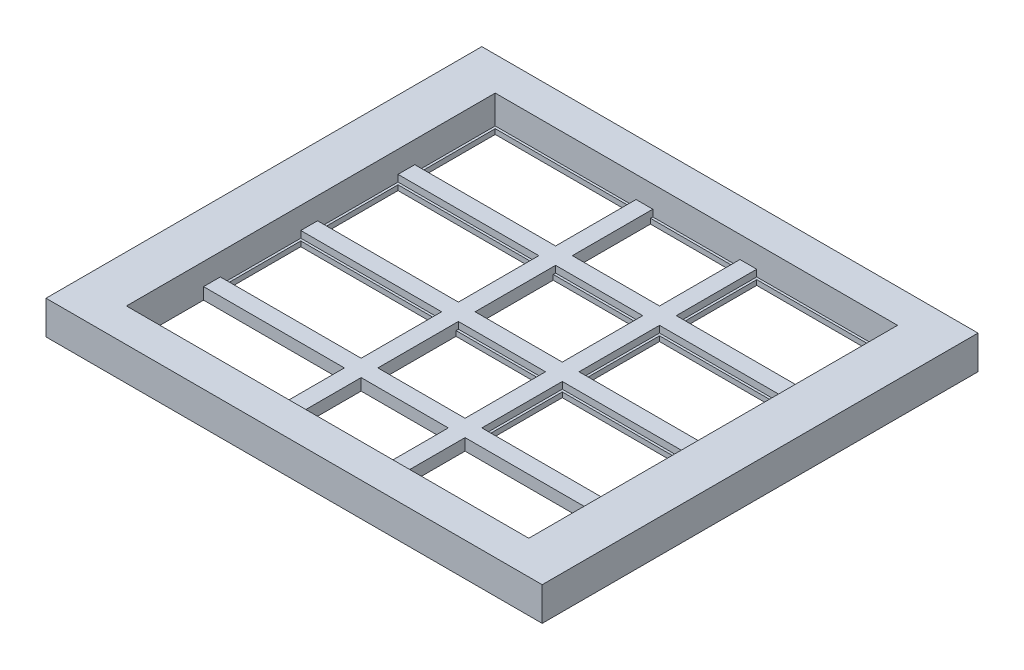
SolidWorks part; units mm, degrees
ref_plane "Front Plane" through (0, 0, 0) normal (0, 0, 1) x (1, 0, 0)
ref_plane "Top Plane" through (0, 0, 0) normal (0, 1, 0) x (1, 0, 0)
ref_plane "Right Plane" through (0, 0, 0) normal (1, 0, 0) x (0, 0, -1)
sketch "Sketch1" plane through (0, 0, 0) normal (0, 1, 0) x (1, 0, 0)
  line L0 (36.2173, -16.1456) -> (36.2173, 113.8544)
  line L1 (50.2173, -6.1456) -> (50.2173, 103.8544)
  line L2 (170.2173, -6.1456) -> (170.2173, 103.8544)
  line L3 (184.2173, -16.1456) -> (184.2173, 113.8544)
  line L4 (36.2173, 113.8544) -> (184.2173, 113.8544)
  line L5 (184.2173, -16.1456) -> (36.2173, -16.1456)
  line L10 (50.2173, 103.8544) -> (170.2173, 103.8544)
  line L12 (170.2173, -6.1456) -> (50.2173, -6.1456)
  line L14 (46.2173, 103.8544) -> (174.2173, 103.8544) construction
  line L15 (174.2173, -6.1456) -> (46.2173, -6.1456) construction
  line L16 (50.2173, -16.1456) -> (50.2173, 113.8544) construction
  line L17 (170.2173, -16.1456) -> (170.2173, 113.8544) construction
  line L18 (46.2173, -6.1456) -> (46.2173, 103.8544) construction
  line L19 (174.2173, -6.1456) -> (174.2173, 103.8544) construction
  line L20 (50.2173, 79.8544) -> (170.2173, 79.8544)
  line L24 (74.2173, 17.8544) -> (74.2173, 79.8544) construction
  line L25 (146.2173, 17.8544) -> (146.2173, 79.8544) construction
  line L26 (146.2173, 17.8544) -> (74.2173, 17.8544) construction
  line L27 (74.2173, 79.8544) -> (146.2173, 79.8544) construction
  line L28 (50.2173, 74.8544) -> (170.2173, 74.8544)
  line L29 (50.2173, 50.8544) -> (170.2173, 50.8544)
  line L30 (50.2173, 45.8544) -> (170.2173, 45.8544)
  line L31 (50.2173, 21.8544) -> (170.2173, 21.8544)
  line L32 (50.2173, 16.8544) -> (170.2173, 16.8544)
  dimension "D1" = 14
  dimension "D2" = 134
  dimension "D3" = 24
  dimension "D4" = 10
  dimension "D5" = 5
  dimension "D6" = 29
  dimension "D7" = 29
extrude "Boss-Extrude2" add sketch "Sketch1" along normal blind 10 contours L5 L3 L4 L0 L2 L12 L1 L10 region at (38.1872, 0, -48.8544)
sketch "Sketch2" plane through (0, 0, 0) normal (0, -1, 0) x (1, 0, 0)
  line L0 (50.2173, -103.8544) -> (170.2173, -103.8544)
  line L1 (50.2173, -103.8544) -> (170.2173, -103.8544) construction
  line L2 (50.2173, 6.1456) -> (170.2173, 6.1456)
  line L3 (170.2173, 6.1456) -> (170.2173, -103.8544) construction
  line L4 (170.2173, 6.1456) -> (50.2173, 6.1456) construction
  line L5 (50.2173, -103.8544) -> (50.2173, 6.1456)
  line L6 (50.2173, 6.1456) -> (50.2173, -103.8544) construction
  line L7 (170.2173, -103.8544) -> (170.2173, 6.1456)
  line L8 (74.2173, -79.8544) -> (146.2173, -79.8544) construction
  line L9 (50.2173, -79.8544) -> (170.2173, -79.8544)
  line L10 (50.2173, -74.8544) -> (170.2173, -74.8544)
  line L11 (74.2173, -79.8544) -> (74.2173, 6.1456) construction
  line L12 (146.2173, -79.8544) -> (146.2173, 6.1456) construction
  line L13 (50.2173, -50.8544) -> (170.2173, -50.8544)
  line L14 (50.2173, -45.8544) -> (170.2173, -45.8544)
  line L15 (50.2173, -21.8544) -> (170.2173, -21.8544)
  line L16 (50.2173, -16.8544) -> (170.2173, -16.8544)
  line L17 (50.9173, -103.1544) -> (169.5173, -103.1544)
  line L18 (169.5173, -103.1544) -> (169.5173, -80.5544)
  line L19 (50.9173, 5.4456) -> (169.5173, 5.4456)
  line L20 (50.9173, -103.1544) -> (50.9173, -80.5544)
  line L21 (50.9173, -74.1544) -> (169.5173, -74.1544)
  line L22 (50.9173, -45.1544) -> (169.5173, -45.1544)
  line L23 (50.9173, -16.1544) -> (169.5173, -16.1544)
  line L24 (50.9173, -80.5544) -> (169.5173, -80.5544)
  line L25 (50.9173, -51.5544) -> (169.5173, -51.5544)
  line L26 (50.9173, -22.5544) -> (169.5173, -22.5544)
  line L27 (50.9173, -74.1544) -> (50.9173, -51.5544)
  line L28 (50.9173, -103.1544) -> (50.9173, 5.4456) construction
  line L29 (50.2173, -74.1544) -> (170.2173, -74.1544) construction
  line L30 (50.2173, -80.5544) -> (170.2173, -80.5544) construction
  line L31 (169.5173, -74.1544) -> (169.5173, -51.5544)
  line L32 (169.5173, -103.1544) -> (169.5173, 5.4456) construction
  line L33 (50.2173, -51.5544) -> (170.2173, -51.5544) construction
  line L34 (169.5173, -45.1544) -> (169.5173, -22.5544)
  line L35 (50.2173, -45.1544) -> (170.2173, -45.1544) construction
  line L36 (50.9173, -45.1544) -> (50.9173, -22.5544)
  line L37 (50.2173, -22.5544) -> (170.2173, -22.5544) construction
  line L38 (169.5173, -16.1544) -> (169.5173, 5.4456)
  line L39 (50.2173, -16.1544) -> (170.2173, -16.1544) construction
  line L40 (50.9173, -16.1544) -> (50.9173, 5.4456)
  line M22 (170.2173, 6.1456) -> (170.2173, -103.8544)
  line M23 (170.2173, -103.8544) -> (50.2173, -103.8544)
  line M24 (50.2173, -103.8544) -> (50.2173, 6.1456)
  line M25 (50.2173, 6.1456) -> (170.2173, 6.1456)
  dimension "D1" = 24
  dimension "D2" = 5
  dimension "D3" = 29
  dimension "D4" = 29
  dimension "D5" = 0.7
  dimension "D6" = 0.7
extrude "Boss-Extrude3" add sketch "Sketch2" against normal blind 1.5 contours L9 L7 L20 L24 L18 L17 M24 M23 | L13 L10 L7 L31 L21 L27 L25 M24 | L15 L14 L7 L22 L36 L26 L34 M24 | L16 L23 L40 L19 L38 M24 M22 M25 | L16 L5 L15 L7 | L14 L5 L13 L7 | L10 L5 L9 L7 region at (50.3397, 0, -91.8544) region at (110.2173, 0, -77.3544) region at (50.3397, 0, -62.8544) region at (110.2173, 0, -48.3544) region at (50.3397, 0, -33.8544) region at (110.2173, 0, -19.3544) region at (50.3395, 0, -5.3544)
sketch "Sketch3" plane through (0, 1.5, 0) normal (0, 1, 0) x (1, 0, 0)
  line L0 (50.2173, 74.8544) -> (170.2173, 74.8544)
  line L3 (50.2173, 79.8544) -> (170.2173, 79.8544)
  line L4 (50.2173, 79.8544) -> (50.2173, 74.8544)
  line L5 (170.2173, 79.8544) -> (170.2173, 74.8544)
  line L6 (50.2173, 45.8544) -> (50.2173, 50.8544)
  line L9 (170.2173, 45.8544) -> (50.2173, 45.8544)
  line L10 (50.2173, 103.8544) -> (50.2173, -6.1456) construction
  line L11 (170.2173, 45.8544) -> (170.2173, 50.8544)
  line L12 (170.2173, -6.1456) -> (170.2173, 103.8544) construction
  line L13 (170.2173, 50.8544) -> (50.2173, 50.8544)
  line L14 (50.2173, 16.8544) -> (50.2173, 21.8544)
  line L16 (170.2173, 16.8544) -> (50.2173, 16.8544)
  line L17 (170.2173, 16.8544) -> (170.2173, 21.8544)
  line L18 (170.2173, -6.1456) -> (170.2173, 103.8544) construction
  line L19 (170.2173, 21.8544) -> (50.2173, 21.8544)
  dimension "D1" = 5
extrude "Boss-Extrude4" add sketch "Sketch3" along normal blind 2 contours L19 L14 L16 L17 | L13 L6 L9 L11 | L5 L0 L4 L3
sketch "Sketch4" plane through (0, 0, 0) normal (0, -1, 0) x (-1, 0, 0)
  line L0 (-50.2173, 103.8544) -> (-50.2173, -6.1456)
  line L1 (-170.2173, -6.1456) -> (-50.2173, -6.1456) construction
  line L2 (-50.2173, -6.1456) -> (-50.2173, 103.8544) construction
  line L3 (-92.2173, 103.8544) -> (-92.2173, -6.1456)
  line L4 (-87.2173, 103.8544) -> (-87.2173, -6.1456)
  line L5 (-87.2173, 103.8544) -> (-92.2173, 103.8544)
  line L6 (-92.2173, -6.1456) -> (-87.2173, -6.1456)
  line L7 (-170.2173, -6.1456) -> (-170.2173, 103.8544)
  line L8 (-128.2173, -6.1456) -> (-128.2173, 103.8544)
  line L9 (-123.2173, -6.1456) -> (-123.2173, 103.8544)
  line L10 (-123.2173, 103.8544) -> (-128.2173, 103.8544)
  line L11 (-128.2173, -6.1456) -> (-123.2173, -6.1456)
  dimension "D1" = 42
  dimension "D2" = 5
  dimension "D3" = 42
  dimension "D4" = 5
extrude "Boss-Extrude5" add sketch "Sketch4" against normal blind 3.5 contours L4 L6 L3 L5 | L9 L10 L8 L11
sketch "Sketch5" plane through (0, 0, 0) normal (0, -1, 0) x (-1, 0, 0)
  line L1 (-92.2173, 80.5544) -> (-92.2173, 103.1544)
  line L2 (-92.2173, 103.1544) -> (-87.2173, 103.1544)
  line L14 (-87.2173, 16.1544) -> (-92.2173, 16.1544)
  line L15 (-92.2173, 16.8544) -> (-92.2173, -6.1456) construction
  line L16 (-92.2173, 16.1544) -> (-92.2173, -5.4456)
  line L17 (-92.2173, -5.4456) -> (-87.2173, -5.4456)
  line L18 (-87.2173, 16.8544) -> (-87.2173, -6.1456) construction
  line L19 (-87.2173, -5.4456) -> (-87.2173, 16.1544)
  line L21 (-87.2173, 22.5544) -> (-92.2173, 22.5544)
  line L22 (-92.2173, 22.5544) -> (-92.2173, 45.1544)
  line L23 (-92.2173, 45.1544) -> (-87.2173, 45.1544)
  line L24 (-87.2173, 103.1544) -> (-87.2173, 80.5544)
  line L25 (-87.2173, 22.5544) -> (-87.2173, 45.1544)
  line L26 (-87.2173, 51.5544) -> (-92.2173, 51.5544)
  line L27 (-92.2173, 51.5544) -> (-92.2173, 74.1544)
  line L28 (-92.2173, 74.1544) -> (-87.2173, 74.1544)
  line L29 (-87.2173, 74.1544) -> (-87.2173, 51.5544)
  line L30 (-87.2173, 80.5544) -> (-92.2173, 80.5544)
extrude "Cut-Extrude1" cut sketch "Sketch5" against normal blind 10
sketch "Sketch6" plane through (0, 1.5, 0) normal (0, 1, 0) x (1, 0, 0)
  line L0 (87.2173, 103.8544) -> (92.2173, 103.8544)
  line L1 (92.2173, 103.8544) -> (92.2173, 103.1544)
  line L2 (92.2173, 103.8544) -> (92.2173, 103.1544) construction
  line L3 (92.2173, 103.1544) -> (87.2173, 103.1544) construction
  line L4 (92.2173, 103.1544) -> (87.2173, 103.1544)
  line L5 (87.2173, 103.1544) -> (87.2173, 103.8544)
  line L6 (92.2173, 80.5544) -> (87.2173, 80.5544)
  line L7 (87.2173, 80.5544) -> (87.2173, 79.8544)
  line L8 (87.2173, 79.8544) -> (92.2173, 79.8544)
  line L9 (92.2173, 79.8544) -> (92.2173, 80.5544)
  line L10 (87.2173, 74.8544) -> (92.2173, 74.8544)
  line L11 (92.2173, 74.8544) -> (92.2173, 74.1544)
  line L12 (92.2173, 74.1544) -> (87.2173, 74.1544) construction
  line L13 (92.2173, 74.1544) -> (123.2173, 74.1544) construction
  line L14 (92.2173, 74.1544) -> (87.2173, 74.1544)
  line L15 (87.2173, 74.8544) -> (87.2173, 74.1544) construction
  line L16 (87.2173, 74.1544) -> (87.2173, 74.8544)
  line L17 (87.2173, 51.5544) -> (92.2173, 51.5544)
  line L18 (92.2173, 51.5544) -> (92.2173, 50.8544)
  line L19 (92.2173, 50.8544) -> (87.2173, 50.8544)
  line L20 (87.2173, 50.8544) -> (87.2173, 51.5544)
  line L21 (92.2173, 45.8544) -> (87.2173, 45.8544)
  line L22 (87.2173, 45.8544) -> (87.2173, 45.1544)
  line L23 (92.2173, 45.1544) -> (87.2173, 45.1544) construction
  line L24 (87.2173, 45.1544) -> (92.2173, 45.1544)
  line L25 (92.2173, 45.1544) -> (92.2173, 45.8544)
  line L26 (87.2173, 22.5544) -> (92.2173, 22.5544)
  line L27 (92.2173, 22.5544) -> (92.2173, 21.8544)
  line L28 (92.2173, 21.8544) -> (87.2173, 21.8544)
  line L29 (87.2173, 21.8544) -> (87.2173, 22.5544)
  line L30 (87.2173, 16.8544) -> (92.2173, 16.8544)
  line L31 (92.2173, 16.8544) -> (92.2173, 16.1544)
  line L32 (92.2173, 16.1544) -> (87.2173, 16.1544) construction
  line L33 (92.2173, 16.1544) -> (87.2173, 16.1544)
  line L34 (87.2173, 16.8544) -> (87.2173, 16.1544) construction
  line L35 (87.2173, 16.1544) -> (87.2173, 16.8544)
  line L36 (87.2173, -5.4456) -> (92.2173, -5.4456)
  line L37 (92.2173, -5.4456) -> (92.2173, -6.1456)
  line L38 (92.2173, -6.1456) -> (87.2173, -6.1456)
  line L39 (87.2173, -6.1456) -> (87.2173, -5.4456)
extrude "Cut-Extrude2" cut sketch "Sketch6" along normal blind 2
sketch "Sketch7" plane through (0, 0, 0) normal (0, -1, 0) x (-1, 0, 0)
  line L0 (-92.2173, 79.8544) -> (-97.2173, 79.8544)
  line L3 (-92.2173, 103.8544) -> (-92.2173, 79.8544)
  line L4 (-97.2173, 103.8544) -> (-97.2173, 79.8544)
  line L5 (-97.2173, 103.8544) -> (-92.2173, 103.8544)
  line L6 (-92.2173, 74.8544) -> (-92.2173, 50.8544)
  line L7 (-97.2173, 74.8544) -> (-97.2173, 50.8544)
  line L8 (-92.2173, 50.8544) -> (-97.2173, 50.8544)
  line L9 (-97.2173, 74.8544) -> (-92.2173, 74.8544)
  line L10 (-97.2173, 16.8544) -> (-97.2173, -6.1456)
  line L11 (-97.2173, 16.8544) -> (-92.2173, 16.8544)
  line L12 (-92.2173, 21.8544) -> (-97.2173, 21.8544)
  line L13 (-97.2173, 45.8544) -> (-92.2173, 45.8544)
  line L15 (-97.2173, 45.8544) -> (-97.2173, 21.8544)
  line L16 (-92.2173, 16.8544) -> (-92.2173, -6.1706)
  line L17 (-92.2173, 45.8544) -> (-92.2173, 21.8544)
  line L18 (-92.2173, -6.1706) -> (-97.2173, -6.1456)
  line L19 (-50.2173, -6.1456) -> (-123.2173, -6.1456) construction
  dimension "D2" = 5
extrude "Boss-Extrude7" add sketch "Sketch7" against normal blind 3.5
sketch "Sketch8" plane through (0, 0, 0) normal (0, -1, 0) x (-1, 0, 0)
  line L0 (-92.2173, 103.1544) -> (-92.2173, 80.5544)
  line L1 (-92.2173, 103.1544) -> (-91.5173, 103.1544)
  line L2 (-50.9173, 103.1544) -> (-92.2173, 103.1544) construction
  line L3 (-91.5173, 103.1544) -> (-91.5173, 80.5544)
  line L4 (-50.9173, 80.5544) -> (-92.2173, 80.5544) construction
  line L5 (-91.5173, 80.5544) -> (-92.2173, 80.5544)
  line L6 (-91.5173, 74.1544) -> (-91.5173, 51.5544)
  line L7 (-92.2173, 74.1544) -> (-91.5173, 74.1544)
  line L8 (-91.5173, 51.5544) -> (-92.2173, 51.5544)
  line L9 (-92.2173, 74.1544) -> (-92.2173, 51.5544)
  line L10 (-91.5173, 22.5544) -> (-92.2173, 22.5544)
  line L11 (-92.2173, 45.1544) -> (-92.2173, 22.5544)
  line L12 (-92.2173, 45.1544) -> (-91.5173, 45.1544)
  line L13 (-91.5173, 45.1544) -> (-91.5173, 22.5544)
extrude "Boss-Extrude8" add sketch "Sketch8" against normal blind 1.5
sketch "Sketch9" plane through (0, 0, 0) normal (0, -1, 0) x (-1, 0, 0)
  line L14 (-50.2173, 16.8544) -> (-92.2173, 16.8544)
  line L15 (-170.2173, -6.1456) -> (-170.2173, 103.8544) construction
  line L16 (-170.2173, 16.8544) -> (-128.2173, 16.8544) construction
  line L36 (-170.2173, -6.1456) -> (-128.2173, -6.1456)
  line L37 (-50.2173, -6.1456) -> (-92.2173, -6.1456) construction
  line L40 (-170.2173, -6.1456) -> (-50.2173, -6.1456) construction
  line L41 (-170.2173, -6.1456) -> (-170.2173, 16.8544)
  line L42 (-50.2173, 16.8544) -> (-50.2173, -6.1456)
  line L43 (-50.9173, 16.1544) -> (-92.2173, 16.1544)
  line L44 (-92.2173, 16.1544) -> (-92.2173, 16.8544)
  line L45 (-92.2173, -6.1456) -> (-92.2173, -5.4456)
  line L46 (-92.2173, -5.4456) -> (-50.9173, -5.4456)
  line L47 (-50.9173, -5.4456) -> (-50.9173, 16.1544)
  line L48 (-97.2173, 16.8544) -> (-97.2173, 16.1544)
  line L49 (-97.2173, 16.1544) -> (-123.2173, 16.1544)
  line L50 (-123.2173, 16.1544) -> (-123.2173, 16.8544)
  line L51 (-123.2173, -5.4456) -> (-97.2173, -5.4456)
  line L52 (-97.2173, -5.4456) -> (-97.2173, -6.1456)
  line L53 (-97.2173, 16.8544) -> (-97.2173, -6.1456) construction
  line L54 (-97.2173, -6.1456) -> (-123.2173, -6.1456)
  line L55 (-123.2173, -6.1456) -> (-123.2173, 16.8544) construction
  line L56 (-123.2173, -6.1456) -> (-123.2173, -5.4456)
  line L57 (-128.2173, 16.8544) -> (-128.2173, 16.1544)
  line L58 (-128.2173, 16.1544) -> (-169.5173, 16.1544)
  line L59 (-169.5173, 16.1544) -> (-169.5173, -5.4456)
  line L60 (-169.5173, -5.4456) -> (-128.2173, -5.4456)
  line L61 (-128.2173, -5.4456) -> (-128.2173, -6.1456)
  line L62 (-97.2173, 16.8544) -> (-123.2173, 16.8544)
  line L63 (-92.2173, -6.1456) -> (-50.2173, -6.1456)
  line L65 (-128.2173, 16.8544) -> (-170.2173, 16.8544)
extrude "Cut-Extrude3" cut sketch "Sketch9" against normal blind 1.5
sketch "Sketch10" plane through (0, 0, 0) normal (0, -1, 0) x (-1, 0, 0)
  line L0 (-128.2173, 103.1544) -> (-128.2173, 80.5544)
  line L1 (-128.2173, 103.1544) -> (-128.9173, 103.1544)
  line L2 (-128.2173, 103.1544) -> (-169.5173, 103.1544) construction
  line L3 (-128.2173, 80.5544) -> (-128.9173, 80.5544)
  line L4 (-128.2173, 80.5544) -> (-169.5173, 80.5544) construction
  line L5 (-128.9173, 80.5544) -> (-128.9173, 103.1544)
  line L6 (-128.9173, 51.5544) -> (-128.9173, 74.1544)
  line L7 (-128.2173, 74.1544) -> (-128.2173, 51.5544)
  line L8 (-128.2173, 51.5544) -> (-128.9173, 51.5544)
  line L9 (-128.2173, 74.1544) -> (-128.9173, 74.1544)
  line L10 (-128.2173, 22.5544) -> (-128.9173, 22.5544)
  line L11 (-128.9173, 22.5544) -> (-128.9173, 45.1544)
  line L12 (-128.2173, 45.1544) -> (-128.2173, 22.5544)
  line L13 (-128.2173, 45.1544) -> (-128.9173, 45.1544)
extrude "Boss-Extrude9" add sketch "Sketch10" against normal blind 1.5
sketch "Sketch11" plane through (0, 0, 0) normal (0, -1, 0) x (-1, 0, 0)
  line L0 (-45.7173, 13.8544) -> (-45.7173, 83.8544)
  line L1 (-40.7173, 13.8544) -> (-40.7173, 83.8544)
  line L2 (-179.7173, 13.8544) -> (-179.7173, 83.8544)
  line L8 (-40.7173, 13.8544) -> (-45.7173, 13.8544)
  line L9 (-40.7173, 83.8544) -> (-45.7173, 83.8544)
  line L10 (-40.7173, -16.1456) -> (-40.7173, 113.8544) construction
  line L11 (-45.7173, -16.1456) -> (-45.7173, 113.8544) construction
  line L12 (-174.7173, 13.8544) -> (-174.7173, 83.8544)
  line L13 (-174.7173, 13.8544) -> (-179.7173, 13.8544)
  line L14 (-174.7173, 83.8544) -> (-179.7173, 83.8544)
extrude "Boss-Extrude10" add sketch "Sketch11" along normal blind 3
